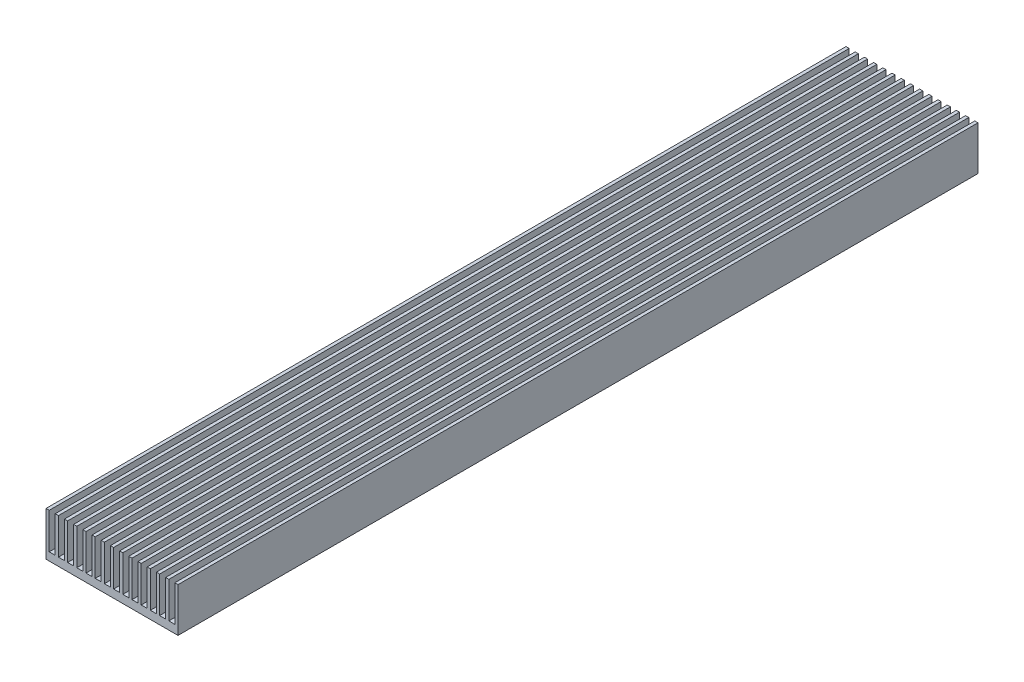
SolidWorks part; units mm, degrees
ref_plane "Ön Düzlem" through (0, 0, 0) normal (0, 0, 1) x (1, 0, 0)
ref_plane "Üst Düzlem" through (0, 0, 0) normal (0, 1, 0) x (1, 0, 0)
ref_plane "Sağ Düzlem" through (0, 0, 0) normal (1, 0, 0) x (0, 0, -1)
sketch "Sketch1" plane through (0, 0, 0) normal (0, 0, 1) x (1, 0, 0)
  line L0 (11.5, 10) -> (11.5, 55)
  line L1 (0, 0) -> (165, 0)
  line L2 (0, 0) -> (0, 10)
  line L3 (4, 10) -> (11.5, 10)
  line L4 (165, 0) -> (165, 10)
  line L6 (0, 10) -> (0, 55)
  line L7 (0, 55) -> (4, 55)
  line L8 (4, 10) -> (4, 55)
  line L10 (15.5, 10) -> (15.5, 55)
  line L11 (11.5, 55) -> (15.5, 55)
  line L12 (23, 10) -> (23, 55)
  line L14 (27, 10) -> (27, 55)
  line L15 (23, 55) -> (27, 55)
  line L16 (34.5, 10) -> (34.5, 55)
  line L18 (38.5, 10) -> (38.5, 55)
  line L19 (34.5, 55) -> (38.5, 55)
  line L20 (46, 10) -> (46, 55)
  line L22 (50, 10) -> (50, 55)
  line L23 (46, 55) -> (50, 55)
  line L24 (57.5, 10) -> (57.5, 55)
  line L26 (61.5, 10) -> (61.5, 55)
  line L27 (57.5, 55) -> (61.5, 55)
  line L28 (69, 10) -> (69, 55)
  line L30 (73, 10) -> (73, 55)
  line L31 (69, 55) -> (73, 55)
  line L32 (80.5, 10) -> (80.5, 55)
  line L34 (84.5, 10) -> (84.5, 55)
  line L35 (80.5, 55) -> (84.5, 55)
  line L36 (92, 10) -> (92, 55)
  line L38 (96, 10) -> (96, 55)
  line L39 (92, 55) -> (96, 55)
  line L40 (103.5, 10) -> (103.5, 55)
  line L42 (107.5, 10) -> (107.5, 55)
  line L43 (103.5, 55) -> (107.5, 55)
  line L44 (115, 10) -> (115, 55)
  line L46 (119, 10) -> (119, 55)
  line L47 (115, 55) -> (119, 55)
  line L48 (126.5, 10) -> (126.5, 55)
  line L50 (130.5, 10) -> (130.5, 55)
  line L51 (126.5, 55) -> (130.5, 55)
  line L52 (138, 10) -> (138, 55)
  line L54 (142, 10) -> (142, 55)
  line L55 (138, 55) -> (142, 55)
  line L56 (149.5, 10) -> (149.5, 55)
  line L58 (153.5, 10) -> (153.5, 55)
  line L59 (149.5, 55) -> (153.5, 55)
  line L60 (161, 10) -> (161, 55)
  line L62 (165, 10) -> (165, 55)
  line L63 (161, 55) -> (165, 55)
  line L78 (15.5, 10) -> (23, 10)
  line L79 (27, 10) -> (34.5, 10)
  line L80 (38.5, 10) -> (46, 10)
  line L81 (50, 10) -> (57.5, 10)
  line L82 (61.5, 10) -> (69, 10)
  line L83 (73, 10) -> (80.5, 10)
  line L84 (84.5, 10) -> (92, 10)
  line L85 (96, 10) -> (103.5, 10)
  line L86 (107.5, 10) -> (115, 10)
  line L87 (119, 10) -> (126.5, 10)
  line L88 (130.5, 10) -> (138, 10)
  line L89 (142, 10) -> (149.5, 10)
  line L90 (153.5, 10) -> (161, 10)
  point P8 (0, 0)
  dimension "D1" = 165
  dimension "D2" = 10
  dimension "D3" = 45
  dimension "D4" = 4
  dimension "D5" = 15
extrude "Boss-Extrude1" add sketch "Sketch1" along normal blind 1000 contours L90 L58 L59 L56 L89 L54 L55 L52 L88 L50 L51 L48 L87 L46 L47 L44 L86 L42 L43 L40 L85 L38 L39 L36 L84 L34 L35 L32 L83 L30 L31 L28 L82 L26 L27 L24 L81 L22 L23 L20 L80 L18 L19 L16 L79 L14 L15 L12 L78 L10 L11 region at (82.5, 22.069, 0)
sketch "Sketch3" plane through (0, 0, 0) normal (0, -1, 0) x (1, 0, 0)
  line L0 (165, 15) -> (165, 150)
  line L1 (165, 1000) -> (165, 0) construction
  line L2 (165, 150) -> (165, 15)
  line L3 (0, 0) -> (165, 0) construction
  line L4 (30, 150) -> (165, 150)
  line L5 (165, 150) -> (130.0594, 19.6) construction
  line L6 (165, 150) -> (69.5406, 54.5406) construction
  line L7 (165, 150) -> (34.6, 115.0594) construction
  line L12 (69.5406, 54.5406) -> (36.581, 21.581) construction
  line L13 (67.7728, 42.1662) -> (74.9913, 49.3847)
  line L14 (57.1662, 52.7728) -> (64.3847, 59.9913)
  line L15 (130.0594, 19.6) -> (120.8907, -14.6181) construction
  arc A0 (165, 15) -> (74.9913, 49.3847) centre (165, 150) cw
  arc A1 (165, 140) -> (155, 150) centre (165, 150) cw construction
  circle A3 centre (62.4695, 47.4695) radius 2.5
  arc A4 (57.1662, 52.7728) -> (67.7728, 42.1662) centre (62.4695, 47.4695) ccw
  arc A5 (64.3847, 59.9913) -> (30, 150) centre (165, 150) cw
  point P10 (0, 0)
  point P22 (0, 0)
  dimension "D2" = 135
  dimension "D3" = 10
  dimension "D5" = 30
  dimension "D8" = 5
  dimension "D10" = 15
  dimension "D4" = 15
  dimension "D6" = 30
  dimension "D9" = 10
sketch "Sketch8" plane through (0, 0, 0) normal (0, -1, 0) x (1, 0, 0)
  line L0 (165, 150) -> (165, 165)
  line L1 (165, 1000) -> (165, 0) construction
  line L2 (165, 165) -> (0, 165)
  line L3 (0, 1000) -> (0, 0) construction
  line L4 (0, 165) -> (0, 0)
  line L5 (0, 0) -> (165, 0)
  line L6 (165, 0) -> (165, 15)
  line L7 (165, 150) -> (30, 150)
  line L8 (74.9913, 49.3847) -> (67.7728, 42.1662)
  line L9 (64.3847, 59.9913) -> (57.1662, 52.7728)
  arc A0 (30, 150) -> (64.3847, 59.9913) centre (165, 150) ccw
  arc A1 (67.7728, 42.1662) -> (57.1662, 52.7728) centre (62.4695, 47.4695) cw
  arc A2 (74.9913, 49.3847) -> (165, 15) centre (165, 150) ccw
  dimension "D1" = 165
